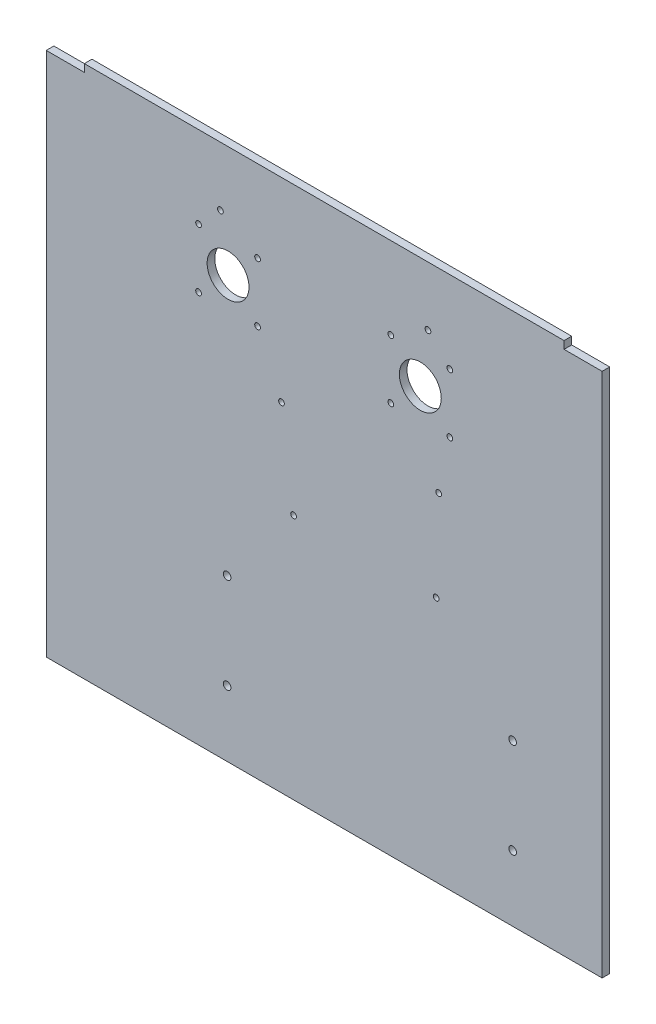
SolidWorks part; units mm, degrees
ref_plane "Front Plane" through (0, 0, 0) normal (0, 0, 1) x (1, 0, 0)
ref_plane "Top Plane" through (0, 0, 0) normal (0, 1, 0) x (1, 0, 0)
ref_plane "Right Plane" through (0, 0, 0) normal (1, 0, 0) x (0, 0, -1)
sketch "Sketch1" plane through (0, 0, 0) normal (0, 0, 1) x (1, 0, 0)
  line L0 (-35, 82.5) -> (-66, 82.5) construction
  line L1 (146, -123.5) -> (-146, -123.5)
  line L2 (146, -123.5) -> (146, 123.5)
  line L3 (146, 123.5) -> (-146, 123.5)
  line L4 (-146, -123.5) -> (-146, 123.5)
  line L5 (146, -123.5) -> (-146, 123.5) construction
  line L6 (146, 123.5) -> (-146, -123.5) construction
  line L7 (-35, 82.5) -> (-35, 113.5) construction
  line L8 (-35, 113.5) -> (-66, 113.5) construction
  line L9 (-66, 82.5) -> (-66, 113.5) construction
  line L10 (-35, 82.5) -> (-66, 113.5) construction
  line L11 (-35, 113.5) -> (-66, 82.5) construction
  line L12 (0, 123.5) -> (0, -133.2191) construction
  line L13 (35, 113.5) -> (66, 82.5) construction
  line L14 (35, 82.5) -> (66, 113.5) construction
  line L15 (66, 82.5) -> (66, 113.5) construction
  line L16 (35, 113.5) -> (66, 113.5) construction
  line L17 (35, 82.5) -> (35, 113.5) construction
  line L18 (35, 82.5) -> (66, 82.5) construction
  line L19 (-175.5662, 125.5) -> (218.0802, 125.5) construction
  line L20 (-146, 123.5) -> (146, 123.5)
  line L21 (-146, 123.5) -> (-146, 156.5)
  line L22 (-146, 156.5) -> (146, 156.5)
  line L23 (146, 123.5) -> (146, 156.5)
  line L24 (0, 156.5) -> (0, 123.5) construction
  line L25 (-146, 140) -> (146, 140) construction
  line L26 (146, 154.5) -> (126, 154.5) construction
  line L27 (-146, 156.5) -> (-126, 156.5)
  line L28 (-146, 156.5) -> (-146, 152.5)
  line L29 (-146, 152.5) -> (-126, 152.5)
  line L30 (-126, 156.5) -> (-126, 152.5)
  line L31 (-136, 152.5) -> (-136, 156.5) construction
  line L32 (-146, 154.5) -> (-126, 154.5) construction
  line L33 (136, 152.5) -> (136, 156.5) construction
  line L34 (126, 156.5) -> (126, 152.5)
  line L35 (146, 152.5) -> (126, 152.5)
  line L36 (146, 156.5) -> (146, 152.5)
  line L37 (146, 156.5) -> (126, 156.5)
  circle A0 centre (-66, 113.5) radius 1.5
  circle A1 centre (-35, 113.5) radius 1.5
  circle A2 centre (66, 82.5) radius 1.5
  circle A3 centre (-50.5, 98) radius 11
  circle A4 centre (-35, 82.5) radius 1.5
  circle A5 centre (-66, 82.5) radius 1.5
  circle A6 centre (35, 82.5) radius 1.5
  circle A7 centre (50.5, 98) radius 11
  circle A8 centre (35, 113.5) radius 1.5
  circle A9 centre (66, 113.5) radius 1.5
  circle A10 centre (99, -39) radius 2
  circle A11 centre (99, -89) radius 2
  circle A12 centre (-51, -39) radius 2
  circle A13 centre (-51, -89) radius 2
  circle A14 centre (60.1213, 54.1951) radius 1.5
  circle A15 centre (-54.5, 125.5) radius 1.5
  circle A16 centre (-16.0787, 5.9351) radius 1.5
  circle A17 centre (58.8513, 5.9351) radius 1.5
  circle A18 centre (-22.4287, 54.1951) radius 1.5
  circle A19 centre (54.5, 125.5) radius 1.5
  point P0 (0, 0)
  point P63 (136, 154.5)
  point P132 (-136, 154.5)
  point P274 (0, 140)
  dimension "D3" = 22
  dimension "D5" = 3
  dimension "D6" = 80
  dimension "D8" = 3
  dimension "D9" = 3
  dimension "D10" = 3
  dimension "D11" = 2
  dimension "D12" = 2
  dimension "D13" = 2
  dimension "D14" = 2
  dimension "D19" = 3
  dimension "D20" = 3
  dimension "D21" = 3
  dimension "D22" = 3
  dimension "D31" = 3
  dimension "D1" = 292
  dimension "D2" = 247
  dimension "D4" = 31
  dimension "D7" = 10
  dimension "D15" = 95
  dimension "D16" = 150
  dimension "D17" = 50
  dimension "D18" = 34.5
  dimension "D23" = 82.55
  dimension "D24" = 48.26
  dimension "D25" = 74.93
  dimension "D26" = 48.26
  dimension "D27" = 69.3049
  dimension "D28" = 85.8787
  dimension "D29" = 33
  dimension "D30" = 2
  dimension "D32" = 54.5
  dimension "D33" = 20
  dimension "D34" = 4
extrude "Boss-Extrude1" add sketch "Sketch1" along normal blind 4 contours L4 L1 L2 L3 A18 A17 A16 A14 A13 A12 A11 A10 A8 A6 A5 A4 A3 A0 A1 A2 A7 A9 | L3 L23 L22 L21 region at (-0.0249, -1.0906, 0) region at (0, 139.7765, 0)
